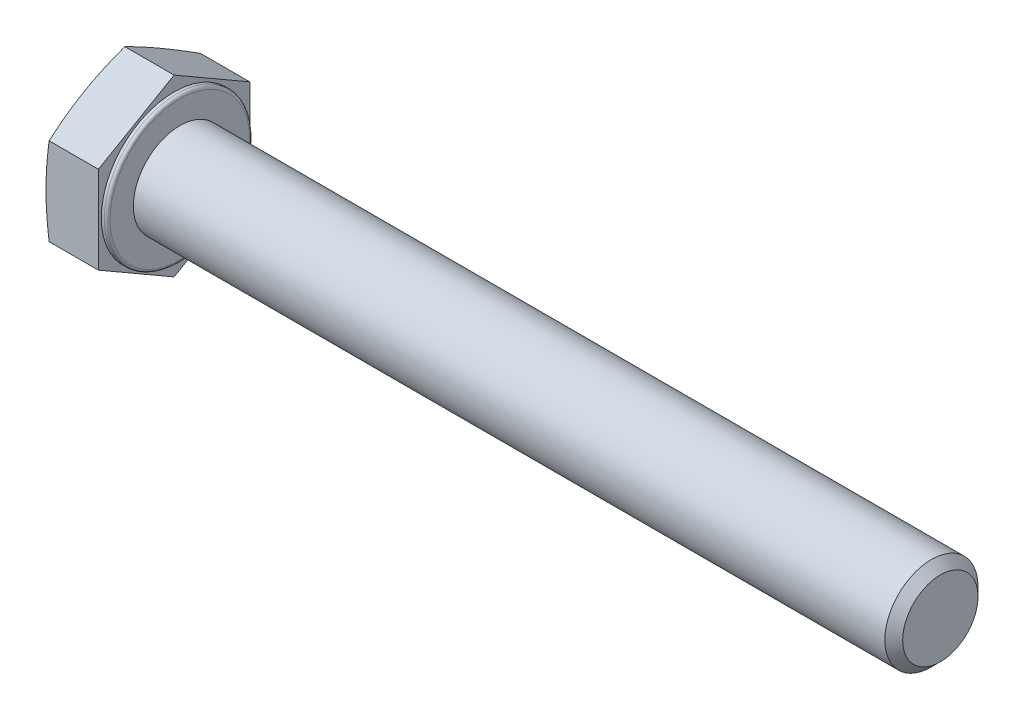
SolidWorks part; units mm, degrees
ref_plane "前视基准面" through (0, 0, 0) normal (0, 0, 1) x (1, 0, 0)
ref_plane "上视基准面" through (0, 0, 0) normal (0, 1, 0) x (1, 0, 0)
ref_plane "右视基准面" through (0, 0, 0) normal (1, 0, 0) x (0, 0, -1)
sketch "草图1" plane through (0, 0, 0) normal (0, 0, 1) x (1, 0, 0)
  line L0 (0, 0) -> (0, 6.5)
  line L1 (0, 6.5) -> (0.3483, 7.8)
  line L2 (0.3483, 7.8) -> (4.5, 7.8)
  line L3 (4.5, 7.8) -> (4.5, 6.25)
  line L4 (4.5, 6.25) -> (4.75, 6.25)
  line L5 (5, 6) -> (5, 4)
  line L6 (5, 4) -> (69.533, 4)
  line L7 (69.533, 4) -> (70.3, 3.233)
  line L8 (70.3, 3.233) -> (70.3, 0)
  line L9 (70.3, 0) -> (0, 0)
  line L10 (70.3, 0) -> (0, 0) construction
  arc A0 (4.75, 6.25) -> (5, 6) centre (4.75, 6) cw
revolve "旋转1" add sketch "草图1" angle 360 about L10 reverse direction yes
cosmetic thread "装饰螺纹线1" parameters "D1"=63.8, "D2"=6.466
sketch "草图2" plane through (0, 0, 0) normal (1, 0, 0) x (0, 0, -1)
  line L0 (-26, 26) -> (-26, -26)
  line L1 (-26, -26) -> (26, -26)
  line L2 (26, -26) -> (26, 26)
  line L3 (26, 26) -> (-26, 26)
  line L4 (-6.5, 3.7528) -> (-6.5, -3.7528)
  line L5 (-6.5, -3.7528) -> (0, -7.5056)
  line L6 (0, -7.5056) -> (6.5, -3.7528)
  line L7 (6.5, -3.7528) -> (6.5, 3.7528)
  line L8 (6.5, 3.7528) -> (0, 7.5056)
  line L9 (0, 7.5056) -> (-6.5, 3.7528)
extrude "切除-拉伸1" cut sketch "草图2" along normal blind 4.5
ref_plane "基准面1" through (4.5, 0, 0) normal (1, 0, 0) x (0, 0, -1)
ref_plane "nut1 XY" through (4.5, 0, 0) normal (1, 0, 0) x (0, 0, -1)
ref_plane "nut1 XZ" through (0, 0, 0) normal (0, -1, 0) x (-1, 0, 0)
ref_plane "nut1 YZ" through (0, 0, 0) normal (0, 0, -1) x (-1, 0, 0)
ref_axis "nut1 X" through (4.5, 0, 80.9) along (0, 0, -1)
ref_axis "nut1 Y" through (4.5, -50, 0) along (0, 1, 0)
ref_axis "nut1 Z" through (80.9, 0, 0) along (-1, 0, 0)
sketch3d "nut1"
  point P0 (4.5, 0, 0)
ref_plane "nut2 XY" through (4.5, 0, 0) normal (1, 0, 0) x (0, 0, -1)
ref_plane "nut2 XZ" through (0, 0, 0) normal (0, -1, 0) x (-1, 0, 0)
ref_plane "nut2 YZ" through (0, 0, 0) normal (0, 0, -1) x (-1, 0, 0)
ref_axis "nut2 X" through (4.5, 0, 80.9) along (0, 0, -1)
ref_axis "nut2 Y" through (4.5, -50, 0) along (0, 1, 0)
ref_axis "nut2 Z" through (80.9, 0, 0) along (-1, 0, 0)
sketch3d "nut2"
  point P0 (4.5, 0, 0)
ref_plane "washer1 XY" through (4.5, 0, 0) normal (1, 0, 0) x (0, 0, -1)
ref_plane "washer1 XZ" through (0, 0, 0) normal (0, -1, 0) x (-1, 0, 0)
ref_plane "washer1 YZ" through (0, 0, 0) normal (0, 0, -1) x (-1, 0, 0)
ref_axis "washer1 X" through (4.5, 0, 80.9) along (0, 0, -1)
ref_axis "washer1 Y" through (4.5, -50, 0) along (0, 1, 0)
ref_axis "washer1 Z" through (80.9, 0, 0) along (-1, 0, 0)
sketch3d "washer1"
  point P0 (4.5, 0, 0)
ref_plane "washer2 XY" through (4.5, 0, 0) normal (1, 0, 0) x (0, 0, -1)
ref_plane "washer2 XZ" through (0, 0, 0) normal (0, -1, 0) x (-1, 0, 0)
ref_plane "washer2 YZ" through (0, 0, 0) normal (0, 0, -1) x (-1, 0, 0)
ref_axis "washer2 X" through (4.5, 0, 80.9) along (0, 0, -1)
ref_axis "washer2 Y" through (4.5, -50, 0) along (0, 1, 0)
ref_axis "washer2 Z" through (80.9, 0, 0) along (-1, 0, 0)
sketch3d "washer2"
  point P0 (4.5, 0, 0)
ref_plane "bolt XY" through (4.5, 0, 0) normal (1, 0, 0) x (0, 0, -1)
ref_plane "bolt XZ" through (0, 0, 0) normal (0, -1, 0) x (-1, 0, 0)
ref_plane "bolt YZ" through (0, 0, 0) normal (0, 0, -1) x (-1, 0, 0)
ref_axis "bolt X" through (4.5, 0, 80.9) along (0, 0, -1)
ref_axis "bolt Y" through (4.5, -50, 0) along (0, 1, 0)
ref_axis "bolt Z" through (80.9, 0, 0) along (-1, 0, 0)
sketch3d "bolt"
  point P0 (4.5, 0, 0)
equation "\"零件重量\"= \"SW-质量\""
